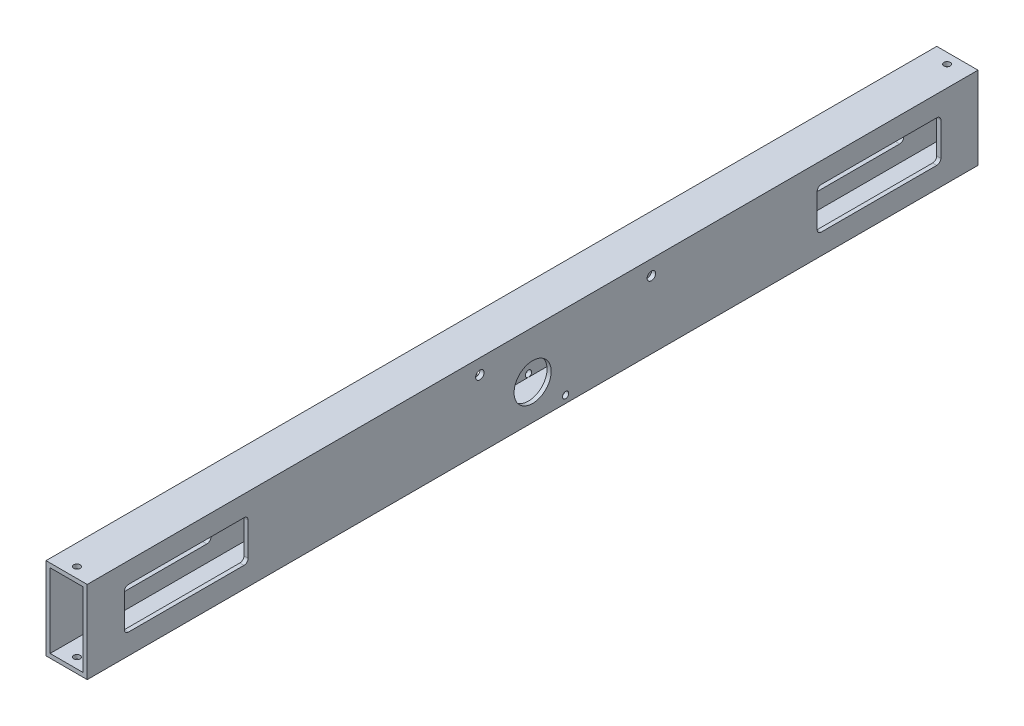
SolidWorks part; units mm, degrees
ref_plane "Front Plane" through (0, 0, 0) normal (0, 0, 1) x (1, 0, 0)
ref_plane "Top Plane" through (0, 0, 0) normal (0, 1, 0) x (1, 0, 0)
ref_plane "Right Plane" through (0, 0, 0) normal (1, 0, 0) x (0, 0, -1)
sketch "Sketch1" plane through (0, 0, 0) normal (0, 0, 1) x (1, 0, 0)
  line L1 (-12.1647, 2.5103) -> (19.5853, 2.5103)
  line L2 (-12.1647, 2.5103) -> (-12.1647, -60.9897)
  line L3 (-12.1647, -60.9897) -> (19.5853, -60.9897)
  line L4 (19.5853, 2.5103) -> (19.5853, -60.9897)
  line L5 (-8.9897, -0.6647) -> (16.4103, -0.6647)
  line L6 (-8.9897, -0.6647) -> (-8.9897, -57.8147)
  line L7 (-8.9897, -57.8147) -> (16.4103, -57.8147)
  line L8 (16.4103, -0.6647) -> (16.4103, -57.8147)
  dimension "D1" = 63.5
  dimension "D2" = 31.75
  dimension "D3" = 3.175
  dimension "D4" = 3.175
  dimension "D5" = 3.175
  dimension "D6" = 3.175
extrude "Boss-Extrude1" add sketch "Sketch1" along normal blind 685.8
sketch "Sketch3" plane through (-12.1647, 0, 0) normal (-1, 0, 0) x (0, 0, 1)
  line L0 (0, 2.5103) -> (0, -60.9897) construction
  line L1 (31.7754, -13.3647) -> (120.6754, -13.3647)
  line L2 (28.6004, -16.5397) -> (28.6004, -41.9397)
  line L3 (31.7754, -45.1147) -> (120.6754, -45.1147)
  line L4 (123.8504, -16.5397) -> (123.8504, -41.9397)
  line L5 (685.8, 2.5103) -> (0, 2.5103) construction
  line L6 (685.8, -60.9897) -> (0, -60.9897) construction
  line L7 (342.9, 2.5103) -> (342.9, -60.9897)
  line L8 (561.9496, -16.5397) -> (561.9496, -41.9397)
  line L9 (654.0246, -45.1147) -> (565.1246, -45.1147)
  line L10 (657.1996, -16.5397) -> (657.1996, -41.9397)
  line L11 (654.0246, -13.3647) -> (565.1246, -13.3647)
  arc A0 (28.6004, -41.9397) -> (31.7754, -45.1147) centre (31.7754, -41.9397) ccw
  arc A1 (120.6754, -45.1147) -> (123.8504, -41.9397) centre (120.6754, -41.9397) ccw
  arc A2 (120.6754, -13.3647) -> (123.8504, -16.5397) centre (120.6754, -16.5397) cw
  arc A3 (31.7754, -13.3647) -> (28.6004, -16.5397) centre (31.7754, -16.5397) ccw
  arc A4 (654.0246, -13.3647) -> (657.1996, -16.5397) centre (654.0246, -16.5397) cw
  arc A5 (565.1246, -13.3647) -> (561.9496, -16.5397) centre (565.1246, -16.5397) ccw
  arc A6 (565.1246, -45.1147) -> (561.9496, -41.9397) centre (565.1246, -41.9397) cw
  arc A7 (657.1996, -41.9397) -> (654.0246, -45.1147) centre (654.0246, -41.9397) cw
  dimension "D5" = 3.175
  dimension "D1" = 28.6004
  dimension "D2" = 15.875
  dimension "D3" = 15.875
  dimension "D4" = 95.25
extrude "Cut-Extrude1" cut sketch "Sketch3" against normal up to surface (31.75 mm away) contours L1 A3 L2 A0 L3 A1 L4 A2 | A7 L10 A4 L11 A5 L8 A6 L9 region at (-12.1647, -29.2397, 76.2254) region at (-12.1647, -29.2397, 609.5746) up to face at (19.5853, -29.2397, 342.9)
sketch "Sketch4" plane through (0, 2.5103, 0) normal (0, 1, 0) x (1, 0, 0)
  line L0 (19.5853, -685.8) -> (-12.1647, -685.8) construction
  line L1 (19.5853, 0) -> (-12.1647, 0) construction
  point P0 (3.7103, -677.8625)
  point P3 (3.7103, -685.8)
  point P4 (3.7103, -7.9375)
  dimension "D1" = 7.9375
  dimension "D2" = 7.9375
hole_wizard "#10 (0.1935) Diameter Hole1" positions "3DSketch1" profile "Sketch5" hole size "#10" standard "ANSI Inch" end condition through all
sketch3d "3DSketch1"
  point P0 (3.7103, 2.5103, 677.8625)
  point P3 (3.7103, 2.5103, 7.9375)
sketch "Sketch5" plane through (3.7103, 2.5103, 677.8625) normal (1, 0, 0) x (0, 0, 1)
  line L0 (0, 0) -> (0, 63.5)
  line L1 (0, 63.5) -> (2.4574, 63.5)
  line L2 (2.4574, 63.5) -> (2.4574, 0)
  line L5 (2.4574, 0) -> (0, 0)
  line L11 (0, -6.35) -> (0, 107.95) construction
  dimension "Thru Hole Dia." = 4.9149
  dimension "Thru Hole Depth" = 63.5
sketch "Sketch6" plane through (19.5853, 0, 0) normal (1, 0, 0) x (0, 0, -1)
  line L0 (-685.8, -60.9897) -> (0, -60.9897) construction
  line L4 (-685.8, -60.9897) -> (-685.8, 2.5103) construction
  circle A0 centre (-342.9, -34.0022) radius 14.2875
  circle A1 centre (-383.54, -8.9197) radius 3.2639
  circle A2 centre (-251.46, -8.9197) radius 3.2639
  circle A3 centre (-317.5, -55.4017) radius 2.413
  point P10 (-342.9, -60.9897)
  dimension "D1" = 28.575
  dimension "D4" = 6.5278
  dimension "D6" = 6.5278
  dimension "D8" = 4.826
  dimension "D2" = 26.9875
  dimension "D3" = 342.9
  dimension "D5" = 40.64
  dimension "D7" = 91.44
  dimension "D9" = 5.588
  dimension "D10" = 25.4
  dimension "D11" = 52.07
  dimension "D12" = 52.07
extrude "Cut-Extrude2" cut sketch "Sketch6" against normal up to surface (31.75 mm away) up to face at (-12.1647, -29.2397, 609.5746)
